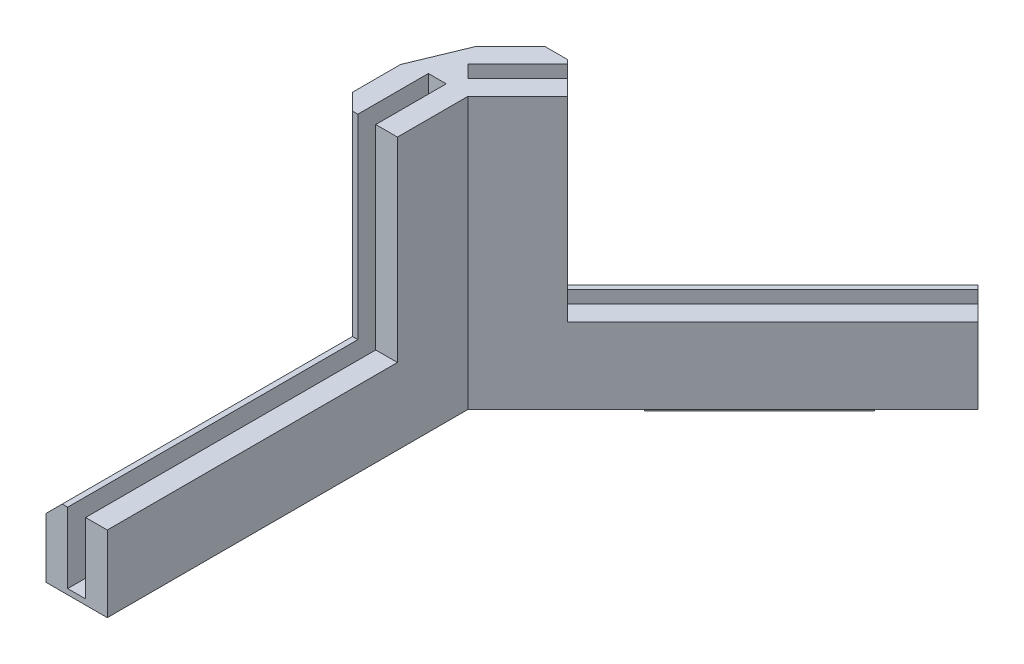
SolidWorks part; units mm, degrees
ref_plane "Front Plane" through (0, 0, 0) normal (0, 0, 1) x (1, 0, 0)
ref_plane "Top Plane" through (0, 0, 0) normal (0, 1, 0) x (1, 0, 0)
ref_plane "Right Plane" through (0, 0, 0) normal (1, 0, 0) x (0, 0, -1)
sketch "Sketch2" plane through (0, 0, 0) normal (0, 1, 0) x (1, 0, 0)
  line L0 (-1.7, -2) -> (-1.7, -15)
  line L1 (-1.7, -15) -> (-5.7, -15)
  line L2 (-5.7, -15) -> (-5.7, -2)
  line L3 (-5.7, -2) -> (-9, -2)
  line L4 (-9, -2) -> (-9, -15)
  line L5 (-9, -15) -> (-13, -15)
  line L7 (-13, -15) -> (-13, 2.6806)
  line L9 (-1.7, -2) -> (-13, 2.6806)
extrude "Boss-Extrude1" add sketch "Sketch2" along normal blind 50
sketch "Sketch3" plane through (0, 0, 2) normal (0, 0, 1) x (1, 0, 0)
  line L0 (-9, 0) -> (-9, 1)
  line L1 (-9, 50) -> (-9, 0) construction
  line L2 (-5.7, 0) -> (-5.7, 1)
  line L3 (-5.7, 50) -> (-5.7, 0) construction
  line L4 (-5.7, 1) -> (-9, 1)
  line L5 (-9, 0) -> (-5.7, 0)
extrude "Boss-Extrude2" add sketch "Sketch3" along normal up to vertex (13 mm away) up to point (-9, 0, 15)
sketch "Sketch5" plane through (0, 0, 15) normal (0, 0, 1) x (1, 0, 0)
  line L0 (-13, 0) -> (-1.7, 0)
  line L1 (-1.7, 50) -> (-1.7, 0) construction
  line L2 (-13, 0) -> (-1.7, 0) construction
  line L3 (-1.7, 0) -> (-1.7, 14)
  line L4 (-13, 0) -> (-13, 14)
  line L5 (-13, 50) -> (-13, 0) construction
  line L6 (-9, 1) -> (-9, 14)
  line L7 (-9, 50) -> (-9, 1) construction
  line L8 (-5.7, 1) -> (-5.7, 14)
  line L9 (-5.7, 50) -> (-5.7, 1) construction
  line L10 (-13, 14) -> (-9, 14)
  line L11 (-9, 1) -> (-5.7, 1)
  line L12 (-5.7, 14) -> (-1.7, 14)
extrude "Boss-Extrude3" add sketch "Sketch5" along normal blind 53.5
sketch "Sketch6" plane through (0, 0, 0) normal (0, -1, 0) x (-1, 0, 0)
  line L0 (1.7, -68.5) -> (4.2, -68.5) construction
  line L1 (13, -68.5) -> (1.7, -68.5) construction
  line L2 (13, -68.5) -> (10.5, -68.5) construction
  line L3 (4.2, -68.5) -> (4.2, -55) construction
  line L4 (10.5, -68.5) -> (10.5, -55) construction
  line L5 (4.2, -55) -> (6.2, -55)
  line L6 (10.5, -55) -> (8.5, -55)
  line L7 (4.2, -55) -> (4.2, -25)
  line L8 (6.2, -55) -> (6.2, -25)
  line L9 (8.5, -55) -> (8.5, -25)
  line L10 (10.5, -55) -> (10.5, -25)
  line L11 (6.2, -25) -> (4.2, -25)
  line L12 (10.5, -25) -> (8.5, -25)
extrude "Boss-Extrude4" add sketch "Sketch6" along normal blind 2
ref_plane "Plane1" through (-0.9561, 0, 2.3081) normal (0.3827, 0, -0.9239) x (-0.9239, 0, -0.3827)
mirror "Mirror1" about plane through (-0.9561, 0, 2.3081) normal (0.3827, 0, -0.9239) of bodies 117
fillet "Chamfer1" radius 14 1 edges at (-13, 25, -2.6806) type face fillet profile chamfer first side face at (7.9447, 21.3333, -23.6254) second side face at (-13, 21.3333, 26.9398)
chamfer "Chamfer2" distance 3 angle 45 4 edges at (-13, 14, 41.75) (-13, 32, 15) (-0.4979, 32, -15.1827) (18.4171, 14, -34.0978)
